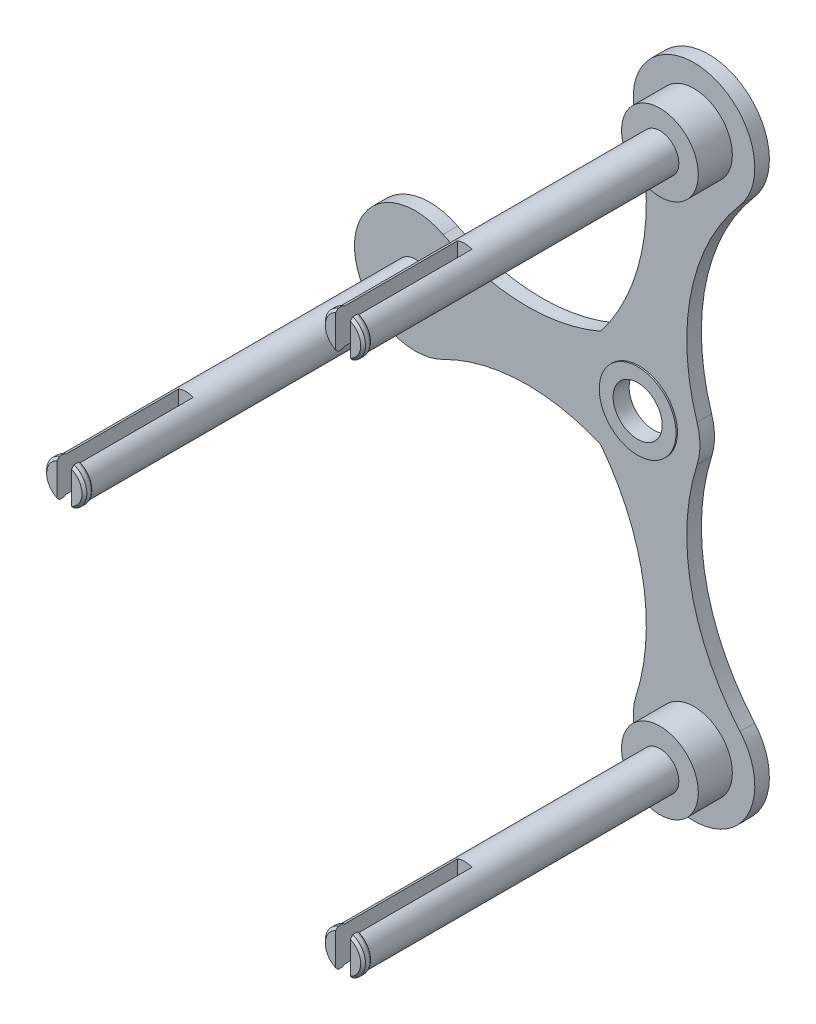
SolidWorks part; units mm, degrees
note: The reader was unsure of these and kept them because the rebuilt part matched: shared geometry of "Esquisse1<3>".
ref_plane "Plan de face" through (0, 0, 0) normal (1, 0, 0) x (0, 1, 0)
ref_plane "Plan de dessus" through (0, 0, 0) normal (0, 0, 1) x (0, 1, 0)
ref_plane "Plan de droite" through (0, 0, 0) normal (0, 1, 0) x (-1, 0, 0)
sketch "Esquisse1" plane through (0, 0, 0) normal (0, 0, 1) x (0, 1, 0)
  line L0 (-55, 0) -> (55, 0) construction
  line L1 (0, 0) -> (0, 104.3558) construction
  line L2 (-55, 0) -> (0, 11.28) construction
  line L3 (0, 57.28) -> (55, 0) construction
  circle A1 centre (-55, 0) radius 3.885
  circle A2 centre (55, 0) radius 3.885
  circle A4 centre (55, 0) radius 12.5
  circle A5 centre (-55, 0) radius 12.5
  circle A7 centre (0, 11.28) radius 5.05
  circle A8 centre (0, 11.28) radius 12.5
  arc A9 (-8.17, 20.7405) -> (-51.2135, 11.9127) centre (-37.5819, 54.7984) cw
  arc A10 (-3.7865, -0.6327) -> (-46.83, -9.4605) centre (-17.4181, -43.5184) ccw
  arc A11 (3.7865, -0.6327) -> (46.83, -9.4605) centre (17.4181, -43.5184) cw
  arc A12 (8.17, 20.7405) -> (51.2135, 11.9127) centre (37.5819, 54.7984) ccw
  circle A13 centre (0, 57.28) radius 3.885
  circle A14 centre (0, 57.28) radius 12.5
  arc A15 (-11.1283, 51.5869) -> (-11.1283, 16.9731) centre (-44.9583, 34.28) cw
  arc A16 (11.1283, 51.5869) -> (11.1283, 16.9731) centre (44.9583, 34.28) ccw
  point P4 (0, 0)
  dimension "D2" = 10.1
  dimension "D3" = 7.77
  dimension "D4" = 25
  dimension "D5" = 11.28
  dimension "D6" = 45
  dimension "D8" = 38
  dimension "D1" = 55
  dimension "D7" = 46
extrude "Boss.-Extru.1" add sketch "Esquisse1" along normal blind 3
extrude "Boss.-Extru.2" add sketch "Esquisse1<3>" along normal blind 73.39 contours A1 | A2 | A13
sketch "Esquisse1<3>" plane through (0, 0, 0) normal (0, 0, 1) x (0, 1, 0) same geometry as "Esquisse1"
sketch "Esquisse2" plane through (0, 0, 3) normal (0, 0, 1) x (1, 0, 0)
  circle A0 centre (0, -55) radius 7.89
  circle A1 centre (0, 55) radius 7.89
  dimension "D1" = 15.78
extrude "Boss.-Extru.3" add sketch "Esquisse2" along normal blind 7
sketch "Esquisse5" plane through (0, 0, 3) normal (0, 0, 1) x (1, 0, 0)
  circle A0 centre (-11.28, 0) radius 7.89
  circle A1 centre (0, 55) radius 7.89 construction
  circle M15 centre (-11.28, 0) radius 5.05
extrude "Boss.-Extru.6" add sketch "Esquisse5" along normal blind 0.3 contours A0 M15
sketch "Esquisse7" plane through (0, 0, 73.39) normal (0, 0, 1) x (1, 0, 0)
  circle A0 centre (-57.28, 0) radius 3.885 construction
  circle A1 centre (-57.28, 0) radius 3.885
  circle A2 centre (0, 55) radius 3.885 construction
  circle A3 centre (0, 55) radius 3.885
  circle A4 centre (0, -55) radius 3.885 construction
  circle A5 centre (0, -55) radius 3.885
  circle A9 centre (-57.28, 0) radius 4.135
  circle A10 centre (0, 55) radius 4.135
  circle A11 centre (0, -55) radius 4.135
  circle M2 centre (-57.28, 0) radius 3.885
  dimension "D1" = 0.25
extrude "Boss.-Extru.7" add sketch "Esquisse7" along normal blind 1.75 contours M2 | A9 M2 | A5 | A11 A5 | A10 A3
chamfer "Chanfrein1" distance 0.5 angle 45 3 edges at (4.135, -55, 75.14) (4.135, 55, 75.14) (-53.145, 0, 75.14)
fillet "Congé1" radius 0.5 3 edges at (4.135, -55, 73.39) (-53.145, 0, 73.39) (4.135, 55, 73.39)
sketch "Esquisse8" plane through (0, 0, 75.14) normal (0, 0, 1) x (1, 0, 0)
  line L1 (-55.78, 5) -> (-58.78, 5)
  line L2 (-55.78, 5) -> (-55.78, -5)
  line L3 (-55.78, -5) -> (-58.78, -5)
  line L4 (-58.78, 5) -> (-58.78, -5)
  line L5 (-55.78, 5) -> (-58.78, -5) construction
  line L6 (-55.78, -5) -> (-58.78, 5) construction
  line L7 (-1.5, -60) -> (1.5, -60)
  line L8 (-1.5, -60) -> (-1.5, -50)
  line L9 (-1.5, -50) -> (1.5, -50)
  line L10 (1.5, -60) -> (1.5, -50)
  line L11 (-1.5, -60) -> (1.5, -50) construction
  line L12 (-1.5, -50) -> (1.5, -60) construction
  line L13 (-1.5, 60) -> (1.5, 60)
  line L14 (-1.5, 60) -> (-1.5, 50)
  line L15 (-1.5, 50) -> (1.5, 50)
  line L16 (1.5, 60) -> (1.5, 50)
  line L17 (-1.5, 60) -> (1.5, 50) construction
  line L18 (-1.5, 50) -> (1.5, 60) construction
  point P0 (-57.28, 0)
  point P6 (0, -55)
  point P12 (0, 55)
  dimension "D1" = 3
  dimension "D2" = 10
extrude "Enlèv. mat.-Extru.2" cut sketch "Esquisse8" against normal blind 25
